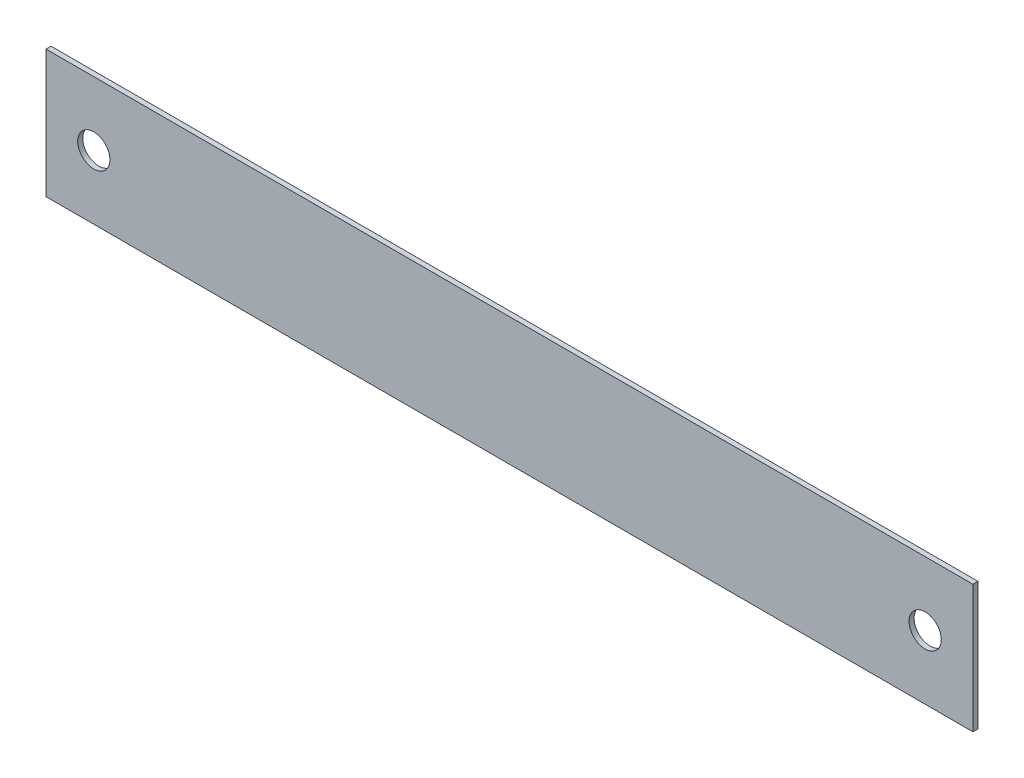
SolidWorks part; units mm, degrees
ref_plane "Front Plane" through (0, 0, 0) normal (0, 0, 1) x (1, 0, 0)
ref_plane "Top Plane" through (0, 0, 0) normal (0, 1, 0) x (1, 0, 0)
ref_plane "Right Plane" through (0, 0, 0) normal (1, 0, 0) x (0, 0, -1)
sketch "Sketch1" plane through (0, 0, 0) normal (0, 0, 1) x (1, 0, 0)
  line L0 (-4.75, -6.35) -> (87.35, -6.35)
  line L1 (87.35, -6.35) -> (87.35, 6.35)
  line L2 (87.35, 6.35) -> (-4.75, 6.35)
  line L3 (-4.75, 6.35) -> (-4.75, -6.35)
  circle A0 centre (0, 0) radius 1.6
  circle A1 centre (82.6, 0) radius 1.6
extrude "Boss-Extrude1" add sketch "Sketch1" along normal blind 0.5
ref_axis "PinHorn" through (0, 0, 0.525) along (0, 0, -1)
ref_plane "PinLeg_px" through (82.6, 0, 0) normal (1, 0, 0) x (0, 0, -1)
ref_axis "PinLeg" through (82.6, 0, 0.525) along (0, 0, -1)
